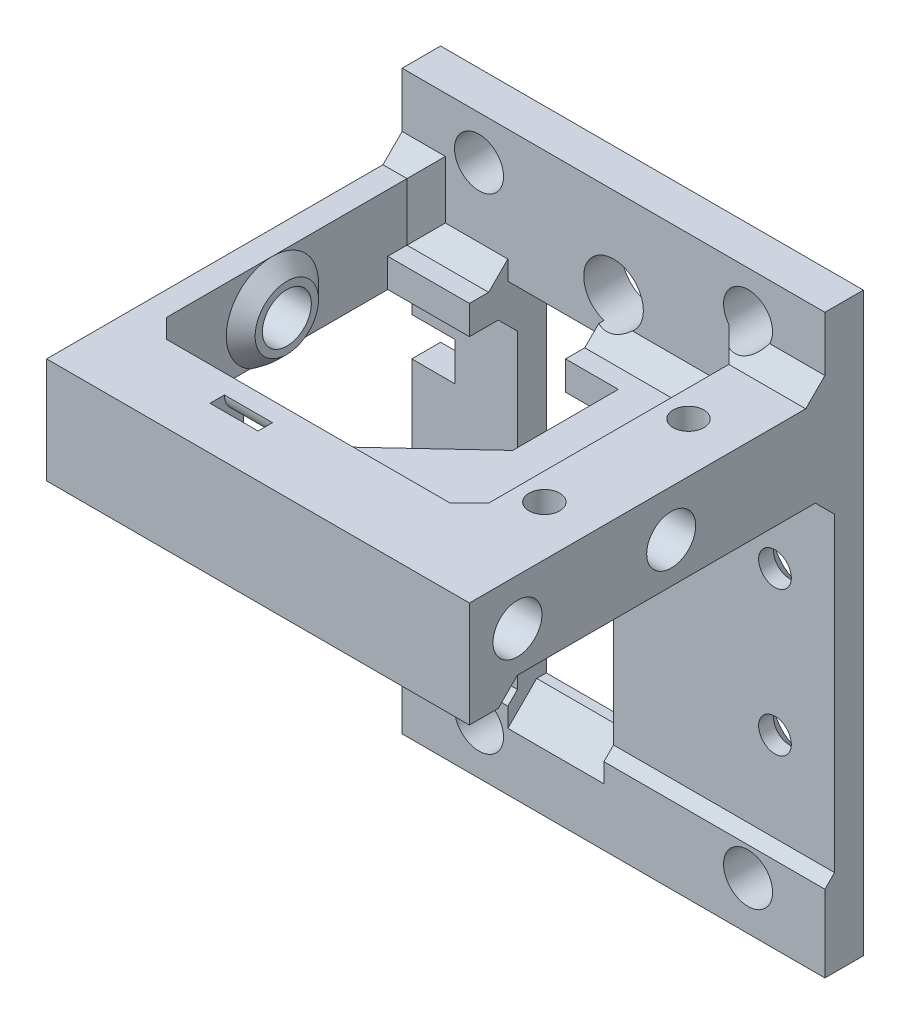
SolidWorks part; units mm, degrees
ref_plane "Front Plane" through (0, 0, 0) normal (0, 0, 1) x (1, 0, 0)
ref_plane "Top Plane" through (0, 0, 0) normal (0, 1, 0) x (1, 0, 0)
ref_plane "Right Plane" through (0, 0, 0) normal (1, 0, 0) x (0, 0, -1)
sketch "Sketch1" plane through (0, 0, 0) normal (0, 1, 0) x (1, 0, 0)
  line L0 (-19.5, 12.5) -> (-19.5, -12.5)
  line L1 (-22, -20.5) -> (22, -20.5)
  line L2 (-22, -20.5) -> (-22, 20.5)
  line L3 (-22, 20.5) -> (22, 20.5)
  line L4 (22, -20.5) -> (22, 20.5)
  line L5 (-22, -20.5) -> (22, 20.5) construction
  line L6 (-22, 20.5) -> (22, -20.5) construction
  line L7 (-19.5, 12.5) -> (4.5, 12.5)
  line L8 (4.5, 12.5) -> (4.5, 1.5)
  line L9 (-19.5, -12.5) -> (-10.5244, -12.5)
  line L10 (-10.5244, -12.5) -> (4.5, 1.5)
  circle A0 centre (16.8, -7.5) radius 1.6
  circle A1 centre (16.8, 7.5) radius 1.6
  point P0 (0, 0)
  dimension "D9" = 3.2
  dimension "D12" = 3.2
  dimension "D1" = 44
  dimension "D2" = 41
  dimension "D3" = 2.5
  dimension "D4" = 25
  dimension "D5" = 8
  dimension "D6" = 24
  dimension "D7" = 11
  dimension "D8" = 5.2
  dimension "D10" = 13
  dimension "D11" = 15
extrude "Boss-Extrude1" add sketch "Sketch1" along normal blind 3
sketch "Sketch2" plane through (0, 3, 0) normal (0, 1, 0) x (1, 0, 0)
  line L0 (-22, 20.5) -> (-22, -20.5) construction
  line L1 (22, 20.5) -> (-22, 20.5)
  line L2 (22, 20.5) -> (22, 16.5)
  line L3 (22, 16.5) -> (-22, 16.5)
  line L4 (-22, 20.5) -> (-22, 16.5)
  dimension "D1" = 4
extrude "Boss-Extrude2" add sketch "Sketch2" along normal blind 13.7
sketch "Sketch3" plane through (0, 0, 0) normal (0, -1, 0) x (1, 0, 0)
  line L0 (22, 20.5) -> (22, -20.5) construction
  line L1 (-22, -20.5) -> (22, -20.5)
  line L2 (-22, -20.5) -> (-22, -17.5)
  line L3 (-22, -17.5) -> (22, -17.5)
  line L4 (22, -20.5) -> (22, -17.5)
  dimension "D1" = 3
extrude "Boss-Extrude3" add sketch "Sketch3" along normal blind 41.3
sketch "Sketch4" plane through (0, 0, 0) normal (0, -1, 0) x (1, 0, 0)
  line L0 (-22, -17.5) -> (-22, 20.5) construction
  line L1 (22, 20.5) -> (-22, 20.5)
  line L2 (22, 20.5) -> (22, 17.5)
  line L3 (22, 17.5) -> (-22, 17.5)
  line L4 (-22, 20.5) -> (-22, 17.5)
  dimension "D1" = 3
extrude "Boss-Extrude4" add sketch "Sketch4" along normal blind 32.5
sketch "Sketch8" plane through (-22, 0, 0) normal (-1, 0, 0) x (0, 0, 1)
  line L0 (-16.5, -35.3) -> (-17.5, -34.3)
  line L1 (-17.5, -41.3) -> (-16.5, -41.3)
  line L2 (-17.5, -41.3) -> (-17.5, -35.3)
  line L3 (-17.5, -35.3) -> (-16.5, -35.3)
  line L4 (-16.5, -41.3) -> (-16.5, -35.3)
  line L5 (-17.5, -41.3) -> (-17.5, 0) construction
  line L6 (-17.5, -34.3) -> (-17.5, -35.3)
  line M5 (-17.5, -41.3) -> (-17.5, 0)
  dimension "D1" = 1
  dimension "D2" = 6
extrude "Boss-Extrude6" add sketch "Sketch8" against normal up to surface (44 mm away) contours L1 L4 L3 M5 | L3 L0 M5 region at (-22, -34.9667, -17.1667) region at (-22, -38.3, -17) up to face at (22, -10.82, -3.3)
sketch "Sketch9" plane through (0, 0, 20.5) normal (0, 0, 1) x (1, 0, 0)
  line L0 (-22, 3) -> (-22, -32.5) construction
  line L1 (3, -26) -> (10, -26)
  line L2 (3, -26) -> (3, -5)
  line L3 (3, -5) -> (10, -5)
  line L4 (10, -26) -> (10, -5)
  line L5 (22, -32.5) -> (-22, -32.5) construction
  line L6 (22, 3) -> (22, -32.5) construction
  circle A0 centre (15.8, -10) radius 1.6
  circle A1 centre (15.8, -25) radius 1.6
  dimension "D5" = 3.2
  dimension "D6" = 3.2
  dimension "D1" = 25
  dimension "D2" = 7
  dimension "D3" = 21
  dimension "D4" = 6.5
  dimension "D7" = 6.2
  dimension "D8" = 6.2
  dimension "D9" = 15
  dimension "D10" = 7.5
extrude "Cut-Extrude2" cut sketch "Sketch9" against normal up to next
sketch "Sketch12" plane through (0, 3, 0) normal (0, 1, 0) x (1, 0, 0)
  line L0 (-22, 16.5) -> (-22, -20.5) construction
  line L1 (22, -20.5) -> (-22, -20.5)
  line L2 (22, -20.5) -> (22, -12.5)
  line L3 (22, -12.5) -> (-22, -12.5)
  line L4 (-22, -20.5) -> (-22, -12.5)
  line L5 (-19.5, -12.5) -> (-10.5244, -12.5) construction
  line L6 (-19.5, 12.5) -> (-19.5, -12.5) construction
  line L7 (-22, 16.5) -> (-19.5, 16.5)
  line L8 (-22, 16.5) -> (-22, -12.5)
  line L9 (-22, -12.5) -> (-19.5, -12.5)
  line L10 (-19.5, 16.5) -> (-19.5, -12.5)
  line L11 (-22, 16.5) -> (22, 16.5) construction
  line L12 (22, -12.5) -> (14, -12.5)
  line L13 (22, -12.5) -> (22, 16.5)
  line L14 (22, 16.5) -> (14, 16.5)
  line L15 (14, -12.5) -> (14, 16.5)
  circle M6 centre (16.8, 7.5) radius 1.6
  circle M7 centre (16.8, -7.5) radius 1.6
  line M11 (-10.5244, -12.5) -> (-19.5, -12.5)
  line M12 (-19.5, -12.5) -> (-19.5, 12.5)
  line M13 (22, 16.5) -> (-22, 16.5)
  line M14 (-22, 16.5) -> (-22, -20.5)
  line M15 (-22, -20.5) -> (22, -20.5)
  line M16 (22, -20.5) -> (22, 16.5)
  dimension "D1" = 8
extrude "Boss-Extrude7" add sketch "Sketch12" along normal blind 6 contours L15 L3 M16 M13 M7 M6 | L3 M16 M11 M14 M15 | L10 L3 M13 M14 M12 region at (0, 3, 16.5) region at (18.0894, 3, -2.149) region at (-20.75, 3, -2)
sketch "Sketch13" plane through (-22, 0, 0) normal (-1, 0, 0) x (0, 0, 1)
  line L0 (20.5, 9) -> (20.5, -32.5) construction
  line L1 (-17.5, 0) -> (17.5, 0) construction
  line L2 (-17.5, -34.3) -> (-17.5, 0) construction
  circle A0 centre (15.5, 4.2) radius 2.55
  circle A1 centre (-0.5, 4.2) radius 2.55
  dimension "D3" = 5.1
  dimension "D5" = 5.1
  dimension "D1" = 5
  dimension "D2" = 4.2
  dimension "D4" = 17
extrude "Cut-Extrude3" cut sketch "Sketch13" against normal blind 6
sketch "Sketch14" plane through (-19.5, 0, 0) normal (1, 0, 0) x (0, 0, -1)
  circle A0 centre (0.5, 4.2) radius 3.3
  circle A1 centre (0.5, 4.2) radius 2.55
  dimension "D1" = 6.6
extrude "Boss-Extrude9" add sketch "Sketch14" along normal blind 1.5
mirror "Mirror1" about plane through (0, 0, 0) normal (1, 0, 0) of "Cut-Extrude3"
sketch "Sketch15" plane through (0, 0, 20.5) normal (0, 0, 1) x (1, 0, 0)
  point P0 (15.8, -10)
  point P1 (15.8, -25)
hole_wizard "CSK for M3 Flat Head Machine Screw1" positions "Sketch18" profile "Sketch19" countersink size "M3" standard "ANSI Metric" end condition through all
sketch "Sketch18" plane through (0, 0, 20.5) normal (0, 0, 1) x (1, 0, 0)
  point P0 (15.8, -10)
  point P3 (15.8, -25)
sketch "Sketch19" plane through (15.8, -10, 20.5) normal (1, 0, 0) x (0, -1, 0)
  line L0 (0, 0) -> (0, 41)
  line L1 (0, 41) -> (1.7, 41)
  line L2 (1.7, 41) -> (1.7, 1.45)
  line L3 (1.7, 1.45) -> (3.15, 0)
  line L5 (3.15, 0) -> (0, 0)
  line L6 (-1.7, 1.45) -> (-3.15, 0) construction
  line L11 (0, -6.35) -> (0, 107.95) construction
  dimension "Thru Hole Dia." = 3.4
  dimension "Thru Hole Depth" = 41
  dimension "Near C'Sink Dia." = 6.3
  dimension "Near C'Sink Angle" = 90
sketch "Sketch20" plane through (0, 0, -20.5) normal (0, 0, -1) x (-1, 0, 0)
  point P0 (-15.8, -10)
  point P1 (-15.8, -25)
hole_wizard "CSK for M3 Flat Head Machine Screw2" positions "Sketch21" profile "Sketch22" countersink size "M3" standard "ANSI Metric" end condition through all
sketch "Sketch21" plane through (0, 0, -20.5) normal (0, 0, -1) x (-1, 0, 0)
  point P0 (-15.8, -10)
  point P3 (-15.8, -25)
sketch "Sketch22" plane through (15.8, -10, -20.5) normal (1, 0, 0) x (0, 1, 0)
  line L0 (0, 0) -> (0, 41)
  line L1 (0, 41) -> (1.7, 41)
  line L2 (1.7, 41) -> (1.7, 1.45)
  line L3 (1.7, 1.45) -> (3.15, 0)
  line L5 (3.15, 0) -> (0, 0)
  line L6 (-1.7, 1.45) -> (-3.15, 0) construction
  line L11 (0, -6.35) -> (0, 107.95) construction
  dimension "Thru Hole Dia." = 3.4
  dimension "Thru Hole Depth" = 41
  dimension "Near C'Sink Dia." = 6.3
  dimension "Near C'Sink Angle" = 90
sketch "Sketch23" plane through (0, 0, -17.5) normal (0, 0, 1) x (1, 0, 0)
  line L0 (22, -34.3) -> (-22, -34.3) construction
  line L1 (-1, 3) -> (-11, 3)
  line L2 (-1, 3) -> (-1, -34.3)
  line L3 (-1, -34.3) -> (-11, -34.3)
  line L4 (-11, 3) -> (-11, -34.3)
  line L5 (-1, 3) -> (-11, -34.3) construction
  line L6 (-1, -34.3) -> (-11, 3) construction
  line L9 (-22, -34.3) -> (-22, 0) construction
  line L11 (14, 3) -> (-10.5244, 3) construction
  point P0 (-6, -15.65)
  dimension "D1" = 10
  dimension "D2" = 16
extrude "Cut-Extrude4" cut sketch "Sketch23" against normal up to next and the other way up to next
chamfer "Chamfer2" distance 1.5 1 edges at (-19.5, 4.2, -3.8)
chamfer "Chamfer3" distance 2 11 edges at (-15.25, 3, -16.5) (6.5, 3, -16.5) (10.5, 0, -17.5) (-16.5, 0, -17.5) (0, 0, 17.5) (18, 9, -16.5) (-20.75, 9, -16.5) (-19.5, 4.5, 12.5) (14, 6, 12.5) (14, 6, -16.5) (-19.5, 6, -16.5)
sketch "Sketch5" plane through (0, 0, -20.5) normal (0, 0, -1) x (-1, 0, 0)
  line L0 (0, -41.3) -> (0, 16.7) construction
  line L1 (22, -41.3) -> (-22, -41.3) construction
  line L2 (-22, 16.7) -> (22, 16.7) construction
  circle A0 centre (-14, -38.3) radius 2.55
  circle A1 centre (14, -38.3) radius 2.55
  circle A2 centre (-14, 12.2) radius 2.55
  circle A3 centre (14, 12.2) radius 2.55
  circle A4 centre (0, 7.4) radius 3.1
  dimension "D1" = 5.1
  dimension "D4" = 5.1
  dimension "D7" = 6.2
  dimension "D2" = 3
  dimension "D3" = 14
  dimension "D5" = 50.5
  dimension "D6" = 9.3
extrude "Cut-Extrude1" cut sketch "Sketch5" against normal up to next
sketch "Sketch24" plane through (-1, 0, 0) normal (-1, 0, 0) x (0, 0, 1)
  line L3 (-17.5, -34.3) -> (-19.5, -34.3)
  line L5 (-16.5, -40.85) -> (-16.5, -35.75) construction
  line L6 (-16.5, -37.3) -> (-16.5, -35.3)
  line L7 (-16.5, -41.3) -> (-16.5, -35.3) construction
  line L8 (-19.5, -34.3) -> (-16.5, -37.3)
  line L9 (-16.5, -35.3) -> (-17.5, -34.3)
extrude "Cut-Extrude9" cut sketch "Sketch24" along normal up to surface (10 mm away) up to face at (-11, -5.36, -16.4)
sketch "Sketch25" plane through (0, 0, 12.5) normal (0, 0, -1) x (-1, 0, 0)
  line L0 (22, 16.7) -> (22, -41.3) construction
  line L1 (9.5, 7) -> (4.5, 7)
  line L2 (9.5, 7) -> (9.5, 5.5)
  line L3 (9.5, 5.5) -> (4.5, 5.5)
  line L4 (4.5, 7) -> (4.5, 5.5)
  line L5 (9.5, 7) -> (4.5, 5.5) construction
  line L6 (9.5, 5.5) -> (4.5, 7) construction
  line L7 (-12, 9) -> (17.5, 9) construction
  point P0 (7, 6.25)
  dimension "D1" = 15
  dimension "D2" = 5
  dimension "D3" = 1.5
  dimension "D4" = 2
sketch "Sketch26" plane through (0, 0, -20.5) normal (0, 0, -1) x (-1, 0, 0)
  line L0 (22, 16.7) -> (22, -41.3) construction
  line L1 (22, -6) -> (17.5, -6)
  line L2 (22, -6) -> (22, -10)
  line L3 (22, -10) -> (17.5, -10)
  line L4 (17.5, -6) -> (17.5, -10)
  line L6 (22.55, 0) -> (-22.55, 0) construction
  dimension "D1" = 6
  dimension "D2" = 4
  dimension "D3" = 4.5
extrude "Cut-Extrude11" cut sketch "Sketch26" against normal up to next
revolve "Cut-Revolve1" cut sketch "Sketch25" angle 90 about axis through (0, 9, 12.5) along (-1, 0, 0)
sketch "Sketch27" plane through (0, -41.3, 0) normal (0, -1, 0) x (1, 0, 0)
  line L1 (-22, -20.5) -> (22, -20.5)
  line L2 (-22, -20.5) -> (-22, -16.5)
  line L3 (-22, -16.5) -> (22, -16.5)
  line L4 (22, -20.5) -> (22, -16.5)
extrude "Boss-Extrude10" add sketch "Sketch27" along normal blind 2
sketch "Sketch28" plane through (0, -32.5, 0) normal (0, -1, 0) x (1, 0, 0)
  line L1 (-22, 17.5) -> (22, 17.5)
  line L2 (-22, 17.5) -> (-22, 20.5)
  line L3 (-22, 20.5) -> (22, 20.5)
  line L4 (22, 17.5) -> (22, 20.5)
extrude "Cut-Extrude13" cut sketch "Sketch28" against normal blind 30.5
